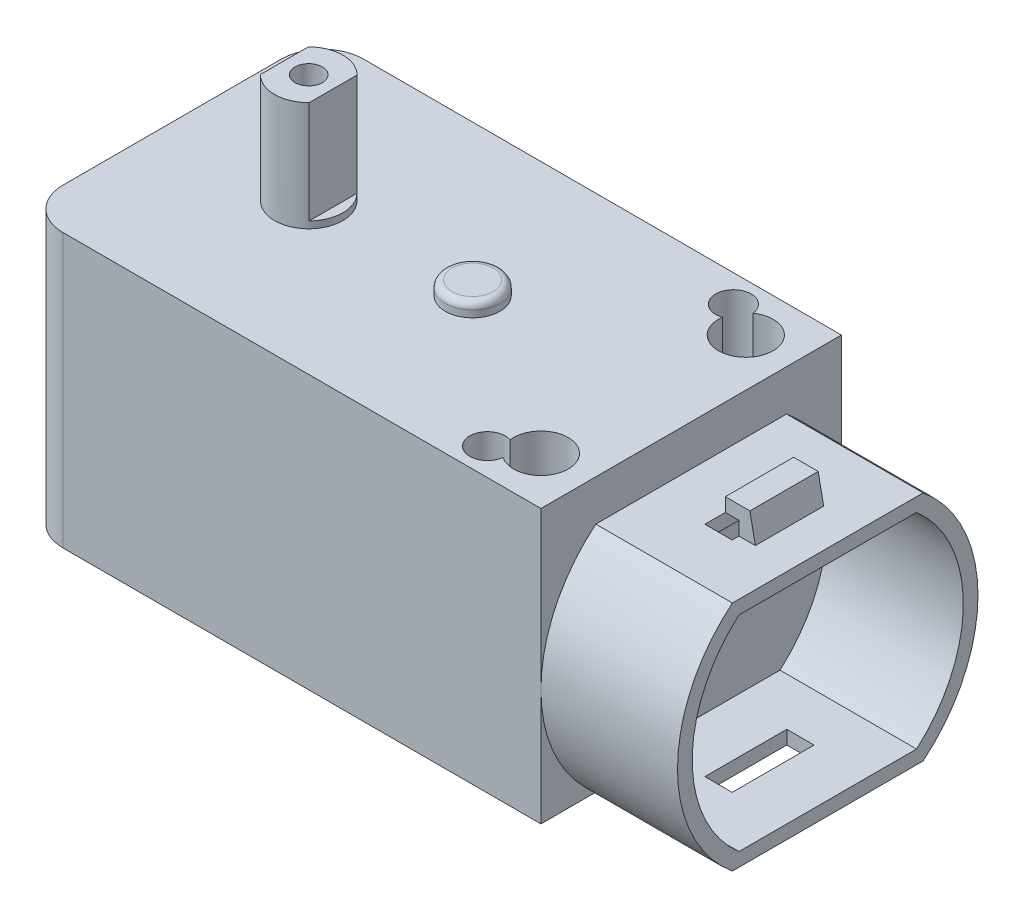
SolidWorks part; units mm, degrees
note: The reader was unsure of these and kept them because the rebuilt part matched: shared geometry of "Croquis1<3>".
ref_plane "Alzado" through (0, 0, 0) normal (0, 0, 1) x (1, 0, 0)
ref_plane "Planta" through (0, 0, 0) normal (0, 1, 0) x (1, 0, 0)
ref_plane "Vista lateral" through (0, 0, 0) normal (1, 0, 0) x (0, 0, -1)
sketch "Croquis1" plane through (0, 0, 0) normal (0, 1, 0) x (1, 0, 0)
  line L0 (-24, 2.5) -> (-29, 2.5)
  line L1 (-21, -11) -> (24, -11)
  line L2 (-24, -8) -> (-24, -2.5)
  line L3 (-21, 11) -> (24, 11)
  line L4 (24, -11) -> (24, 11)
  line L5 (-24, -11) -> (24, 11) construction
  line L6 (-24, 11) -> (24, -11) construction
  line L7 (-29, 2.5) -> (-29, -2.5)
  line L8 (-29, -2.5) -> (-24, -2.5)
  line L9 (-24, 2.5) -> (-24, 8)
  line L10 (-24, 2.5) -> (-24, -2.5)
  circle A0 centre (-26.5, 0) radius 1.25
  arc A1 (-21, -11) -> (-24, -8) centre (-21, -8) cw
  arc A2 (-24, 8) -> (-21, 11) centre (-21, 8) cw
  point P0 (0, 0)
  dimension "D4" = 2.5
  dimension "D6" = 3
  dimension "D1" = 48
  dimension "D2" = 22
  dimension "D3" = 5
  dimension "D5" = 5
extrude "Saliente-Extruir1" add sketch "Croquis1" along normal mid plane 20 contours A2 L9 L10 L2 A1 L1 L4 L3
extrude "Saliente-Extruir2" add sketch "Croquis1<3>" along normal mid plane 3 contours L10 L0 L7 L8 A0
sketch "Croquis1<3>" plane through (0, 0, 0) normal (0, 1, 0) x (1, 0, 0) same geometry as "Croquis1"
sketch "Croquis5" plane through (0, 10, 0) normal (0, 1, 0) x (1, 0, 0)
  line L0 (-24, 2.5) -> (-24, -2.5) construction
  circle A0 centre (-14, 0) radius 2.5
  dimension "D1" = 5
  dimension "D2" = 10
extrude "Saliente-Extruir3" add sketch "Croquis5" along normal blind 8
sketch "Croquis6" plane through (0, 18, 0) normal (0, 1, 0) x (1, 0, 0)
  line L0 (-15.7854, 1.75) -> (-15.7854, -1.75)
  line L1 (-12.2146, 1.75) -> (-12.2146, -1.75)
  circle A0 centre (-14, 0) radius 2.5 construction
  circle A2 centre (-14, 0) radius 2.5 construction
  arc A3 (-15.7854, 1.75) -> (-15.7854, -1.75) centre (-14, 0) ccw
  arc A5 (-12.2146, -1.75) -> (-12.2146, 1.75) centre (-14, 0) ccw
  dimension "D1" = 3.5
  dimension "D2" = 3.5
extrude "Cortar-Extruir7" cut sketch "Croquis6" against normal blind 7.5
mirror "Simetría2" about plane through (0, 0, 0) normal (0, 1, 0) of "Saliente-Extruir3", "Cortar-Extruir7"
sketch "Croquis7" plane through (0, 18, 0) normal (0, 1, 0) x (1, 0, 0)
  circle A0 centre (-14, 0) radius 1
extrude "Cortar-Extruir8" cut sketch "Croquis7" against normal blind 36
sketch "Croquis9" plane through (0, 10, 0) normal (0, 1, 0) x (1, 0, 0)
  line L0 (-21, 11) -> (24, 11) construction
  line L1 (0, 0) -> (31.4022, 0) construction
  circle A0 centre (8.0911, 9) radius 1.3
  circle A1 centre (8.0911, -9) radius 1.3
  dimension "D1" = 2.6
  dimension "D2" = 2
sketch "Croquis13" plane through (24, 0, 0) normal (1, 0, 0) x (0, 0, -1)
  line L0 (-6.5, 6) -> (6.5, 6)
  line L2 (-11, 10) -> (-11, -10) construction
  line L4 (-6.9821, -10) -> (-11, -10)
  line L5 (-6.9821, 7) -> (6.9821, 7)
  line L6 (-6.5, -9) -> (6.5, -9)
  line L7 (-11, -10) -> (-11, 10)
  line L8 (-11, 10) -> (11, 10)
  line L9 (11, 10) -> (11, -10)
  line L10 (11, -10) -> (6.9821, -10)
  line L11 (0, 6) -> (0, -9) construction
  arc A0 (-6.5, 6) -> (-6.5, -9) centre (0, -1.5) ccw
  arc A1 (-6.9821, 7) -> (-6.9821, -10) centre (0, -1.5) ccw
  arc A2 (6.5, -9) -> (6.5, 6) centre (0, -1.5) ccw
  arc A3 (6.9821, -10) -> (6.9821, 7) centre (0, -1.5) ccw
  point P4 (0, 6)
  line M2 (-11, -10) -> (11, -10)
  line M3 (11, -10) -> (11, 10)
  line M4 (11, 10) -> (-11, 10)
  line M5 (-11, 10) -> (-11, -10)
  dimension "D2" = 13
  dimension "D3" = 15
  dimension "D5" = 1
extrude "Cortar-Extruir18" cut sketch "Croquis13" against normal blind 10 contours A3 L9 A1 L5 M4 M5 | A3 M2 M3 | L11 L0 A0 L6 | L0 L11 L6 A2 | A1 L7 M2
extrude "Cortar-Extruir16" cut sketch "Croquis9" against normal blind 36
sketch "Croquis11" plane through (0, 10, 0) normal (0, 1, 0) x (1, 0, 0)
  line L0 (-24, 2.5) -> (-24, -2.5) construction
  circle A0 centre (-2, 0) radius 2
  dimension "D2" = 4
  dimension "D1" = 22
extrude "Saliente-Extruir4" add sketch "Croquis11" along normal blind 1
fillet "Redondeo1" radius 0.5 1 edges at (-2, 11, 2)
sketch "Croquis12" plane through (0, -10, 0) normal (0, -1, 0) x (1, 0, 0)
  line L0 (19.8, 0) -> (-19.8, 0) construction
  circle A0 centre (-22.0308, 9.1179) radius 0.6
  circle A1 centre (10.9692, 9.1179) radius 0.6
  circle A2 centre (10.9692, -9.1179) radius 0.6
  circle A3 centre (-22.0308, -9.1179) radius 0.6
  dimension "D1" = 1.2
  dimension "D2" = 2
extrude "Cortar-Extruir17" cut sketch "Croquis12" against normal blind 9
sketch "Croquis14" plane through (0, -10, 0) normal (0, -1, 0) x (-1, 0, 0)
  line L0 (0, 0) -> (-30.7156, 0) construction
sketch "Croquis15" plane through (0, 10, 0) normal (0, 1, 0) x (1, 0, 0)
  line L0 (0, 0) -> (6.8584, 0) construction
  line L1 (0, 0) -> (30.7156, 0) construction
  line L2 (14, 11) -> (14, -11) construction
  line L4 (-21, 11) -> (14, 11) construction
  circle A0 centre (10.5, 7.5) radius 2
  circle A2 centre (10.5, -7.5) radius 2
  dimension "D1" = 3.5
  dimension "D2" = 3.5
extrude "Cortar-Extruir21" cut sketch "Croquis15" against normal blind 5
sketch "Croquis16" plane through (14, 0, 0) normal (1, 0, 0) x (0, 0, -1)
  circle A0 centre (0, -1.5) radius 2.5
extrude "Cortar-Extruir22" cut sketch "Croquis16" against normal blind 10
sketch "Croquis17" plane through (0, 7, 0) normal (0, 1, 0) x (1, 0, 0)
  line L0 (18, 3.0021) -> (18, -2.9979)
  line L1 (18, -2.9979) -> (20, -2.9979)
  line L2 (20, -2.9979) -> (20, 3.0021)
  line L3 (20, 3.0021) -> (18, 3.0021)
  line L5 (14, 6.9821) -> (24, 6.9821) construction
  line L6 (14, -6.9821) -> (14, 6.9821) construction
  point P6 (20, 0.0021)
  dimension "D1" = 2
  dimension "D2" = 6
  dimension "D3" = 6.98
  dimension "D4" = 4
extrude "Cortar-Extruir23" cut sketch "Croquis17" against normal blind 20
sketch "Croquis18" plane through (0, 0, 0) normal (0, 0, 1) x (1, 0, 0)
  line L0 (21.2, 7) -> (20.8, 9)
  line L2 (14, 7) -> (24, 7) construction
  line L3 (20.8, 9) -> (19, 9)
  line L4 (19, 9) -> (19, 8)
  line L5 (19, 8) -> (20, 8)
  line L6 (20, 8) -> (20, 7)
  line L7 (20, 7) -> (21.2, 7)
  dimension "D1" = 1.2
  dimension "D2" = 1
  dimension "D3" = 1
  dimension "D4" = 1
  dimension "D5" = 1.8
extrude "Saliente-Extruir5" add sketch "Croquis18" along normal mid plane 5
ref_plane "Plano5" through (0, -1.5, 0) normal (0, 1, 0) x (1, 0, 0)
mirror "Simetría3" about plane through (0, -1.5, 0) normal (0, 1, 0) of "Saliente-Extruir5"
